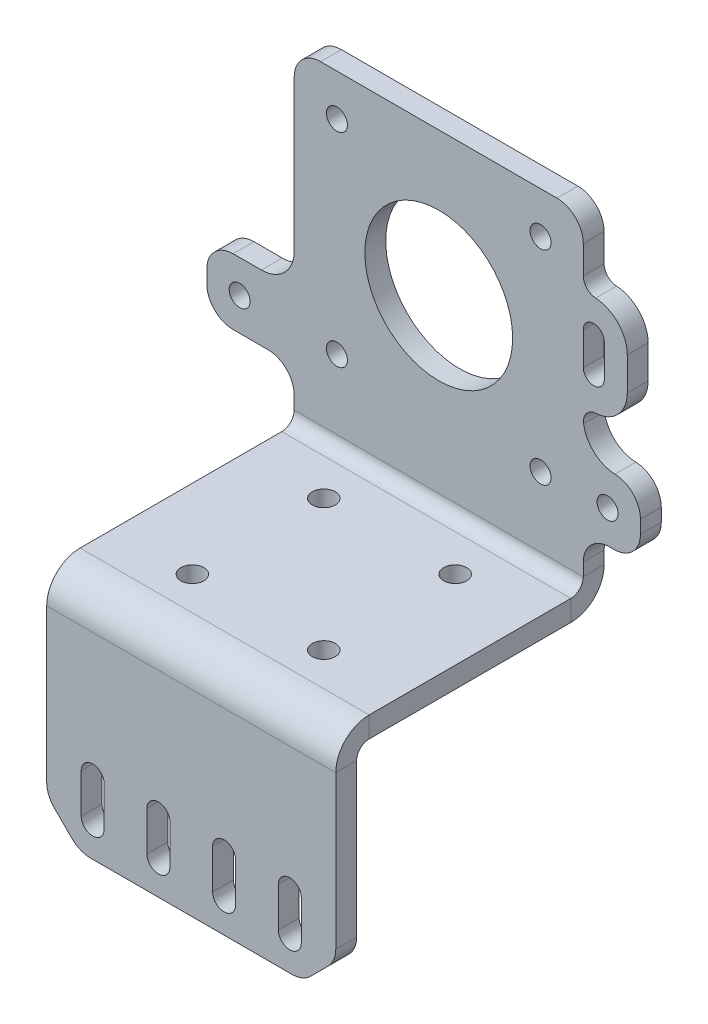
SolidWorks part; units mm, degrees
note: The reader was unsure of these and kept them because the rebuilt part matched: flange length of "Edge-Flange1", "Edge-Flange2".
material "5052-H32"
ref_plane "Front Plane" through (0, 0, 0) normal (0, 0, 1) x (1, 0, 0)
ref_plane "Top Plane" through (0, 0, 0) normal (0, 1, 0) x (1, 0, 0)
ref_plane "Right Plane" through (0, 0, 0) normal (1, 0, 0) x (0, 0, -1)
sketch "Sketch1" plane through (0, 0, 0) normal (0, 1, 0) x (1, 0, 0)
  line L1 (-22, -17) -> (22, -17)
  line L2 (-22, -17) -> (-22, 17.5)
  line L3 (-22, 17.5) -> (22, 17.5)
  line L4 (22, -17) -> (22, 17.5)
  line L5 (0, 17.5) -> (0, -17) construction
  line L7 (-10, -10) -> (10, -10) construction
  line L8 (-10, -10) -> (-10, 10) construction
  line L9 (-10, 10) -> (10, 10) construction
  line L10 (10, -10) -> (10, 10) construction
  line L11 (0, 10) -> (0, -10) construction
  line L12 (-10, 0) -> (10, 0) construction
  circle A0 centre (-10, 10) radius 1.75
  circle A1 centre (10, 10) radius 1.75
  circle A2 centre (10, -10) radius 1.75
  circle A3 centre (-10, -10) radius 1.75
  point P0 (0, 0)
  point P4 (0, 0)
  dimension "D3" = 3.5
  dimension "D1" = 17
  dimension "D2" = 44
  dimension "D4" = 20
  dimension "D5" = 17.5
base flange "Base-Flange1" sketch "Sketch1" thickness 3.175 reverse thickness direction no parameters "D1"=1.905
edge flange "Edge-Flange1" sketch "Sketch8" flange angle 90 flange length 53 flange position material outside bend radius 1.905 thickness 3.175 relief rectangular parameters "D6"=10
sketch "Sketch8" plane through (0, 0, -17.5) normal (0, 0, -1) x (-1, 0, 0)
  line L0 (-22, 0) -> (22, 0) construction
  line L1 (-22, 0) -> (22, 0)
  line L2 (-22, 0) -> (-22, 49.825)
  line L3 (-22, 49.825) -> (22, 49.825)
  line L4 (22, 49.825) -> (22, 0)
bend "EdgeBend1" bend radius 1.905 bend angle 90 parameters "D5"=1
edge flange "Edge-Flange2" sketch "Sketch11" flange angle 90 flange length 35 flange position material outside bend radius 1.905 thickness 3.175 relief rectangular parameters "D6"=10
sketch "Sketch11" plane through (0, -3.175, 17) normal (0, 0, 1) x (-1, 0, 0)
  line L0 (22, 0) -> (-22, 0) construction
  line L1 (22, 0) -> (-22, 0)
  line L2 (-22, 0) -> (-22, 31.825)
  line L3 (-22, 31.825) -> (22, 31.825)
  line L4 (22, 31.825) -> (22, 0)
bend "EdgeBend2" bend radius 1.905 bend angle 90 parameters "D5"=2
sketch "Sketch12" plane through (0, 0, -20.675) normal (0, 0, -1) x (-1, 0, 0)
  line L0 (22, 49.825) -> (-22, 49.825) construction
  line L1 (22, 0) -> (-22, 0) construction
  point P2 (0, 49.825)
  line B0 (0, 43.5) -> (0, 12.5) construction
  line B1 (15.5, 28) -> (-15.5, 28) construction
  circle B2 centre (0, 28) radius 11.25
  circle B3 centre (15.5, 43.5) radius 1.6
  circle B4 centre (15.5, 12.5) radius 1.6
  circle B5 centre (-15.5, 12.5) radius 1.6
  circle B6 centre (-15.5, 43.5) radius 1.6
  dimension "D1" = 28
sketch_block_instance "Block-Nema17 Bolt Pattern-1"
sketch_block "Block-Nema17 Bolt Pattern" parameters "D1"=22.5, "D2"=3.2, "D3"=31, "D4"=31
extrude "Cut-Extrude1" cut sketch "Sketch12" against normal up to next normal cut yes
sketch "Sketch13" plane through (0, 0, 20.175) normal (0, 0, 1) x (1, 0, 0)
  line L0 (-22, -27.175) -> (22, -27.175) construction
  line L1 (-22, -5.08) -> (-22, -35) construction
  line L2 (22, -35) -> (22, -5.08) construction
  line L3 (-22, -3.175) -> (22, -3.175) construction
  line L4 (-5, -30.175) -> (-5, -24.175) construction
  line L5 (-6.75, -30.175) -> (-6.75, -24.175)
  line L6 (-3.25, -30.175) -> (-3.25, -24.175)
  line L7 (0, -27.175) -> (0, -35) construction
  line L8 (-22, -35) -> (22, -35) construction
  line L9 (-15, -30.175) -> (-15, -24.175) construction
  line L10 (-16.75, -30.175) -> (-16.75, -24.175)
  line L11 (-13.25, -30.175) -> (-13.25, -24.175)
  line L12 (15, -30.175) -> (15, -24.175) construction
  line L13 (16.75, -30.175) -> (16.75, -24.175)
  line L14 (13.25, -30.175) -> (13.25, -24.175)
  line L15 (5, -30.175) -> (5, -24.175) construction
  line L16 (6.75, -30.175) -> (6.75, -24.175)
  line L17 (3.25, -30.175) -> (3.25, -24.175)
  arc A0 (-6.75, -30.175) -> (-3.25, -30.175) centre (-5, -30.175) ccw
  arc A1 (-3.25, -24.175) -> (-6.75, -24.175) centre (-5, -24.175) ccw
  arc A2 (-16.75, -30.175) -> (-13.25, -30.175) centre (-15, -30.175) ccw
  arc A3 (-13.25, -24.175) -> (-16.75, -24.175) centre (-15, -24.175) ccw
  arc A4 (16.75, -30.175) -> (13.25, -30.175) centre (15, -30.175) cw
  arc A5 (13.25, -24.175) -> (16.75, -24.175) centre (15, -24.175) cw
  arc A6 (6.75, -30.175) -> (3.25, -30.175) centre (5, -30.175) cw
  arc A7 (3.25, -24.175) -> (6.75, -24.175) centre (5, -24.175) cw
  point P10 (-5, -27.175)
  point P22 (-15, -27.175)
  point P29 (15, -27.175)
  point P36 (5, -27.175)
  dimension "D2" = 1.75
  dimension "D1" = 24
  dimension "D3" = 6
  dimension "D5" = 10
  dimension "D6" = 5
extrude "Cut-Extrude2" cut sketch "Sketch13" against normal up to next normal cut yes
chamfer "Chamfer1" distance 5 angle 45 2 edges at (-22, -35, 18.5875) (22, -35, 18.5875)
sketch "Sketch14" plane through (0, 0, -20.675) normal (0, 0, -1) x (-1, 0, 0)
  line L0 (-30.7, 17.85) -> (-30.7, 7.85)
  line L1 (35.3, 7.85) -> (35.3, 17.85)
  line L2 (0, 28) -> (0, 12.85) construction
  line L3 (30.3, 12.85) -> (-25.7, 12.85) construction
  line L4 (-22, 17.85) -> (-30.7, 17.85)
  line L5 (-22, 49.825) -> (-22, 1.905) construction
  line L6 (22, 17.85) -> (35.3, 17.85)
  line L7 (22, 1.905) -> (22, 49.825) construction
  line L8 (22, 7.85) -> (35.3, 7.85)
  line L9 (-22, 7.85) -> (-30.7, 7.85)
  line L10 (-22, 17.85) -> (-22, 7.85)
  line L11 (22, 17.85) -> (22, 7.85)
  circle A0 centre (30.3, 12.85) radius 1.6
  circle A1 centre (-25.7, 12.85) radius 1.6
  circle A2 centre (0, 28) radius 11.25 construction
  point P0 (0, 28)
  dimension "D6" = 5
  dimension "D1" = 3.2
  dimension "D2" = 56
  dimension "D4" = 15.15
  dimension "D5" = 25.7
  dimension "D7" = 5
  dimension "D8" = 5
extrude "Boss-Extrude1" add sketch "Sketch14" against normal up to surface (3.175 mm away) up to face at (-15.5, 41.9, -17.5)
fillet "Fillet2" radius 5 2 edges at (22, 17.85, -19.0875) (-22, 17.85, -19.0875)
fillet "Fillet3" radius 4 12 edges at (-35.3, 7.85, -19.0875) (-35.3, 17.85, -19.0875) (30.7, 7.85, -19.0875) (30.7, 17.85, -19.0875) (-22, 49.825, -19.0875) (22, 49.825, -19.0875) (-22, 7.85, -19.0875) (22, 7.85, -19.0875) (-22, -30, 18.5875) (-17, -35, 18.5875) (17, -35, 18.5875) (22, -30, 18.5875)
sketch "Sketch19" plane through (0, 0, -20.675) normal (0, 0, -1) x (-1, 0, 0)
  line L0 (-23.6, 34.5) -> (-23.6, 29.5) construction
  line L2 (-22, 34.5) -> (-22, 29.5)
  line L3 (-25.2, 34.5) -> (-25.2, 29.5)
  line L4 (-22, 45.825) -> (-22, 22.85) construction
  line L5 (-18.5, 34.5) -> (-18.5, 29.5)
  line L6 (-28.7, 34.5) -> (-28.7, 29.5)
  line L8 (-22, 41.5887) -> (-22, 22.85)
  arc A0 (-22, 34.5) -> (-25.2, 34.5) centre (-23.6, 34.5) ccw
  arc A1 (-25.2, 29.5) -> (-22, 29.5) centre (-23.6, 29.5) ccw
  arc A2 (-28.7, 29.5) -> (-18.5, 29.5) centre (-23.6, 29.5) ccw
  arc A3 (-18.5, 34.5) -> (-28.7, 34.5) centre (-23.6, 34.5) ccw
  circle A4 centre (0, 28) radius 11.25 construction
  arc A5 (-23.8873, 39.5919) -> (-22, 41.5887) centre (-24, 41.5887) ccw
  arc A6 (-22.0533, 22.1219) -> (-23.9103, 24.4094) centre (-24.032, 22.4132) ccw
  arc A7 (-26.8333, 17.8528) -> (-22, 22.85) centre (-27, 22.85) ccw construction
  arc A8 (-22.0533, 22.1219) -> (-22, 22.85) centre (-27, 22.85) ccw
  point P2 (-23.6, 32)
  dimension "D1" = 1.6
  dimension "D2" = 5
  dimension "D5" = 4
  dimension "D4" = 4
  dimension "D3" = 3.5
extrude "Boss-Extrude3" add sketch "Sketch19" against normal up to surface (3.175 mm away) up to face at (-15.5, 41.9, -17.5)
sketch "Bend-Lines1" [suppressed] plane through (0, 0, 0) normal (0, 1, 0) x (1, 0, 0)
sketch "Bounding-Box1" [suppressed] plane through (0, 0, 0) normal (0, 1, 0) x (1, 0, 0)
sheet metal parameters "Sheet-Metal1" thickness 3.175 parameters "D1"=1.905
flat pattern "Flat-Pattern1" [suppressed]
sketch "Bend-Lines2" plane through (0, 0, 0) normal (0, 1, 0) x (1, 0, 0)
sketch "Bounding-Box2" [suppressed] plane through (0, 0, 0) normal (0, 1, 0) x (1, 0, 0)
sheet metal parameters "Sheet-Metal2" thickness 3.175 parameters "D1"=1.905
flat pattern "Flat-Pattern1" [suppressed]
sketch "Bend-Lines2" plane through (0, 0, 0) normal (0, 1, 0) x (1, 0, 0)
sketch "Bounding-Box2" [suppressed] plane through (0, 0, 0) normal (0, 1, 0) x (1, 0, 0)
bend of the flat pattern "Flatten-<EdgeBend1>1"
sheet metal parameters "Sheet-Metal3" thickness 3.175 parameters "D1"=1.905
flat pattern "Flat-Pattern1" [suppressed]
sketch "Bend-Lines2" plane through (0, 0, 0) normal (0, 1, 0) x (1, 0, 0)
sketch "Bounding-Box2" [suppressed] plane through (0, 0, 0) normal (0, 1, 0) x (1, 0, 0)
bend of the flat pattern "Flatten-<EdgeBend1>1"
bend of the flat pattern "Flatten-<EdgeBend2>1"
sheet metal parameters "Sheet-Metal4" thickness 3.175 parameters "D1"=1.905
flat pattern "Flat-Pattern1" [suppressed]
sketch "Bend-Lines2" plane through (0, 0, 0) normal (0, 1, 0) x (1, 0, 0)
sketch "Bounding-Box2" [suppressed] plane through (0, 0, 0) normal (0, 1, 0) x (1, 0, 0)
bend of the flat pattern "Flatten-<EdgeBend1>1"
bend of the flat pattern "Flatten-<EdgeBend2>1"
sheet metal parameters "Sheet-Metal5" thickness 3.175 parameters "D1"=1.905
flat pattern "Flat-Pattern1"
sketch "Bend-Lines2" plane through (0, 0, 0) normal (0, 1, 0) x (1, 0, 0)
  line L0 (-22, -18.838) -> (22, -18.838) construction
  line L1 (22, 18.838) -> (-22, 18.838) construction
  line L2 (-22, -18.838) -> (22, -18.838) construction
  line L3 (22, 18.838) -> (-22, 18.838) construction
sketch3d "Bounding-Box2" [suppressed]
  line L0 (22, -36.501, 0) -> (22, 66.501, 0) construction
  line L1 (-22, -36.501, 0) -> (-22, 66.501, 0) construction
  line L2 (22, -36.501, 0) -> (-22, -36.501, 0) construction
  line L3 (22, 66.501, 0) -> (-22, 66.501, 0) construction
bend of the flat pattern "Flatten-<EdgeBend1>1"
bend of the flat pattern "Flatten-<EdgeBend2>1"
sheet metal parameters "Sheet-Metal6" thickness 3.175 parameters "D1"=1.905
flat pattern "Flat-Pattern1" [suppressed]
sketch "Bend-Lines2" plane through (0, 0, 0) normal (0, 1, 0) x (1, 0, 0)
  line L0 (-22, -19.338) -> (22, -19.338) construction
  line L1 (22, 19.338) -> (-22, 19.338) construction
  line L2 (-22, -19.338) -> (22, -19.338) construction
  line L3 (22, 19.338) -> (-22, 19.338) construction
sketch3d "Bounding-Box2" [suppressed]
  line L0 (30.7, -37.001, 0) -> (30.7, 67.001, 0) construction
  line L1 (-35.3, -37.001, 0) -> (-35.3, 67.001, 0) construction
  line L2 (30.7, -37.001, 0) -> (-35.3, -37.001, 0) construction
  line L3 (30.7, 67.001, 0) -> (-35.3, 67.001, 0) construction
bend of the flat pattern "Flatten-<EdgeBend1>1"
bend of the flat pattern "Flatten-<EdgeBend2>1"
sketch "Sketch16-1" [suppressed] plane through (0, 0, 17.001) normal (0, 1, 0) x (1, 0, 0)
  line L0 (0, -29.725) -> (0, -5.08) construction
  line L3 (-22, 0) -> (22, 0) construction
  point P6 (-5.25, -23)
  point P10 (5.25, -23)
  dimension "D1" = 5.25
  dimension "D2" = 23
sheet metal parameters "Sheet-Metal9" thickness 3.175 parameters "D1"=1.905
flat pattern "Flat-Pattern1" [suppressed]
sketch "Bend-Lines2" plane through (0, 0, 0) normal (0, 1, 0) x (1, 0, 0)
  line L0 (-22, -19.338) -> (22, -19.338) construction
  line L1 (22, 19.338) -> (-22, 19.338) construction
  line L2 (-22, -19.338) -> (22, -19.338) construction
  line L3 (22, 19.338) -> (-22, 19.338) construction
sketch3d "Bounding-Box2" [suppressed]
  line L0 (30.7, -37.001, 0) -> (30.7, 67.001, 0) construction
  line L1 (-35.3, -37.001, 0) -> (-35.3, 67.001, 0) construction
  line L2 (30.7, -37.001, 0) -> (-35.3, -37.001, 0) construction
  line L3 (30.7, 67.001, 0) -> (-35.3, 67.001, 0) construction
bend of the flat pattern "Flatten-<EdgeBend1>1"
bend of the flat pattern "Flatten-<EdgeBend2>1"
sketch "Sketch16-1" [suppressed] plane through (0, 0, 17.001) normal (0, 1, 0) x (1, 0, 0)
  line L0 (0, -29.725) -> (0, -5.08) construction
  line L3 (-22, 0) -> (22, 0) construction
  point P6 (-5.25, -23)
  point P10 (5.25, -23)
  dimension "D1" = 5.25
  dimension "D2" = 23
equation "\"D6@Sketch13\"=\"D5@Sketch13\"/2"
equation "\"D8@Sketch14\"=\"D7@Sketch14\""
